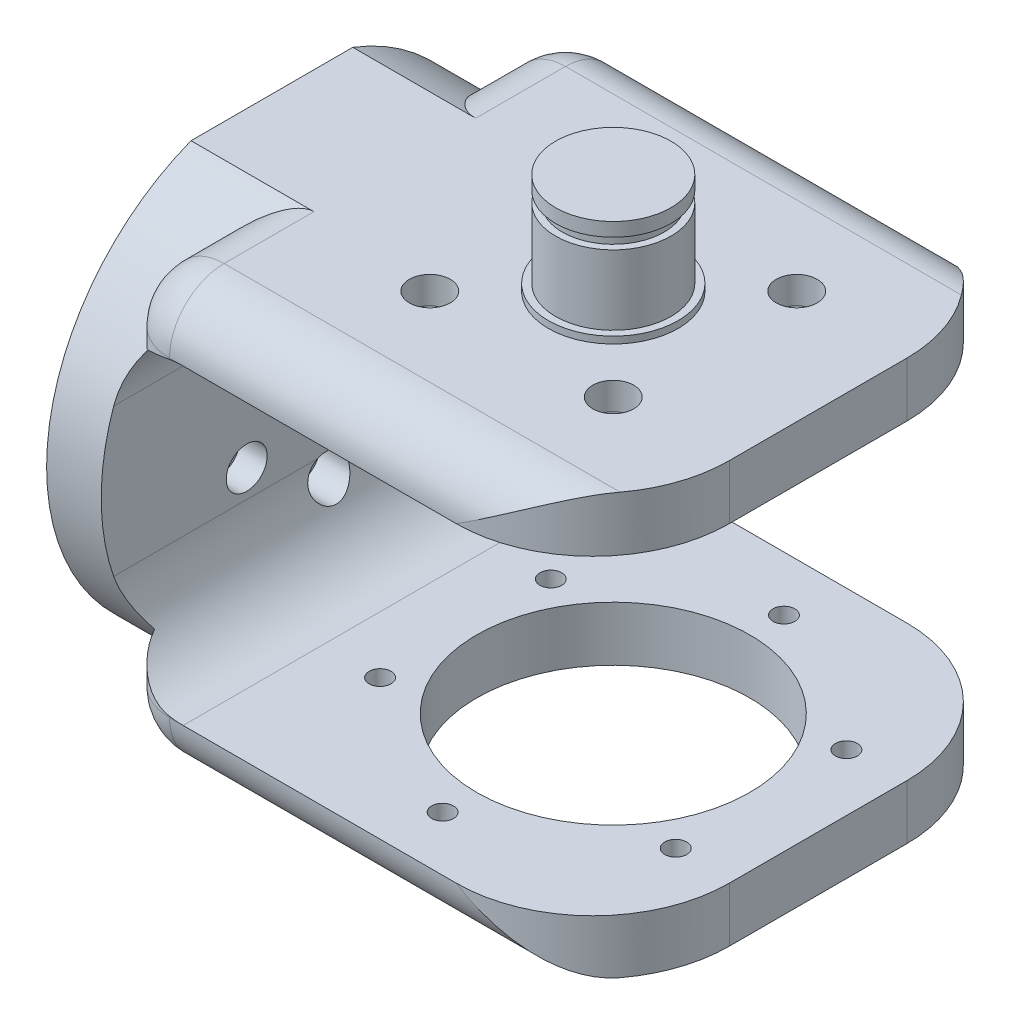
SolidWorks part; units mm, degrees
material "PETG-CF"
ref_plane "Front Plane" through (0, 0, 0) normal (0, 0, 1) x (1, 0, 0)
ref_plane "Top Plane" through (0, 0, 0) normal (0, 1, 0) x (1, 0, 0)
ref_plane "Right Plane" through (0, 0, 0) normal (1, 0, 0) x (0, 0, -1)
sketch "草图1" plane through (0, 0, 0) normal (0, 1, 0) x (1, 0, 0)
  line L1 (40, -33) -> (-40, -33)
  line L2 (40, -33) -> (40, 33)
  line L3 (40, 33) -> (-40, 33)
  line L4 (-40, -33) -> (-40, 33)
  line L5 (40, -33) -> (-40, 33) construction
  line L6 (40, 33) -> (-40, -33) construction
  point P0 (0, 0)
  dimension "D1" = 66
  dimension "D2" = 80
extrude "凸台-拉伸1" add sketch "草图1" along normal blind 8
sketch "草图2" plane through (0, 8, 0) normal (0, 1, 0) x (1, 0, 0)
  line L0 (-40, -33) -> (40, -33) construction
  line L1 (-32, -33) -> (-40, -33)
  line L2 (-32, -33) -> (-32, 33)
  line L3 (-32, 33) -> (-40, 33)
  line L4 (-40, -33) -> (-40, 33)
  line L5 (-32, -33) -> (-40, 33) construction
  line L6 (-32, 33) -> (-40, -33) construction
  point P0 (-36, 0)
  dimension "D1" = 8
extrude "凸台-拉伸2" add sketch "草图2" along normal blind 53.6
sketch "草图5" plane through (-32, 0, 0) normal (1, 0, 0) x (0, 0, -1)
  line L0 (-33, 61.6) -> (-33, 8) construction
  line L1 (33, 53.6) -> (-33, 53.6)
  line L2 (33, 53.6) -> (33, 61.6)
  line L3 (33, 61.6) -> (-33, 61.6)
  line L4 (-33, 53.6) -> (-33, 61.6)
  line L5 (33, 53.6) -> (-33, 61.6) construction
  line L6 (33, 61.6) -> (-33, 53.6) construction
  line L7 (33, 61.6) -> (33, 8) construction
  line L9 (-33, 61.6) -> (33, 61.6) construction
  point P0 (0, 57.6)
  dimension "D1" = 8
extrude "凸台-拉伸3" add sketch "草图5" along normal through all
sketch "草图4" plane through (0, 8, 0) normal (0, 1, 0) x (1, 0, 0)
  line L0 (-40, 33) -> (-40, -33) construction
  line L2 (40, -33) -> (40, 33) construction
  circle A0 centre (10, 0) radius 25 construction
  circle A1 centre (10, 25) radius 1.6
  circle A2 centre (-11.6506, 12.5) radius 1.6
  circle A3 centre (-11.6506, -12.5) radius 1.6
  circle A4 centre (10, -25) radius 1.6
  circle A5 centre (10, 0) radius 20
  circle A6 centre (31.6506, -12.5) radius 1.6
  circle A7 centre (31.6506, 12.5) radius 1.6
  point P17 (10, 0)
  point P22 (-40, 0)
  dimension "D3" = 50
  dimension "D4" = 3.2
  dimension "D6" = 40
  dimension "D1" = 30
  dimension "D5" = 6
extrude "切除-拉伸1" cut sketch "草图4" against normal through all contours A5 | A2 | A1 | A4 | A3 | A7 | A6
sketch "草图7" plane through (0, 61.6, 0) normal (0, 1, 0) x (1, 0, 0)
  line L0 (40, 33) -> (40, -33) construction
  line L2 (40, 33) -> (40, -33) construction
  line L3 (10, 0) -> (-3.435, 13.435) construction
  line L4 (10, 0) -> (10, 19) construction
  circle A0 centre (10, 0) radius 19 construction
  circle A5 centre (-3.435, 13.435) radius 1.6
  circle A6 centre (23.435, 13.435) radius 1.6
  circle A7 centre (23.435, -13.435) radius 1.6
  circle A8 centre (-3.435, -13.435) radius 1.6
  point P10 (40, 0)
  point P18 (10, 0)
  point P20 (10, 0)
  dimension "D1" = 38
  dimension "D4" = 45
  dimension "D5" = 3.2
  dimension "D3" = 30
  dimension "D6" = 4
extrude "切除-拉伸3" cut sketch "草图7" against normal up to next
sketch "草图8" plane through (0, 61.6, 0) normal (0, 1, 0) x (1, 0, 0)
  circle A0 centre (10, 0) radius 8.45
  dimension "D1" = 16.9
extrude "凸台-拉伸4" add sketch "草图8" along normal blind 14.8
ref_plane "基准面1" through (0, 74.4, 0) normal (0, 1, 0) x (1, 0, 0)
sketch "草图10" plane through (0, 74.4, 0) normal (0, 1, 0) x (1, 0, 0)
  circle A0 centre (10, 0) radius 8.45
  circle A1 centre (10, 0) radius 7.45
  dimension "D1" = 14.9
extrude "切除-拉伸4" cut sketch "草图10" against normal blind 1.6
ref_plane "基准面2" through (-36, 0, 0) normal (-1, 0, 0) x (0, 0, 1)
sketch "草图14" plane through (0, 61.6, 0) normal (0, 1, 0) x (1, 0, 0)
  circle A0 centre (-3.435, 13.435) radius 3
  circle A1 centre (23.435, 13.435) radius 3
  circle A2 centre (23.435, -13.435) radius 3
  circle A3 centre (-3.435, -13.435) radius 3
  point P12 (10, 0)
  dimension "D1" = 6
  dimension "D2" = 4
extrude "切除-拉伸6" cut sketch "草图14" against normal blind 4
sketch "草图15" plane through (0, 0, 0) normal (0, -1, 0) x (1, 0, 0)
  circle A0 centre (-11.6506, 12.5) radius 3
  circle A1 centre (10, 25) radius 3
  circle A2 centre (31.6506, 12.5) radius 3
  circle A3 centre (31.6506, -12.5) radius 3
  circle A4 centre (10, -25) radius 3
  circle A5 centre (-11.6506, -12.5) radius 3
  point P15 (10, 0)
  dimension "D1" = 6
  dimension "D2" = 6
extrude "切除-拉伸7" cut sketch "草图15" against normal blind 4
sketch "草图16" plane through (0, 61.6, 0) normal (0, 1, 0) x (1, 0, 0)
  circle A0 centre (10, 0) radius 9.5
  dimension "D1" = 19
extrude "凸台-拉伸5" add sketch "草图16" along normal blind 1
sketch "Sketch1" plane through (-40, 0, 0) normal (-1, 0, 0) x (0, 0, 1)
  line L0 (33, 61.6) -> (33, 0) construction
  circle A0 centre (0, 30.8) radius 18
  point P8 (33, 30.8)
  dimension "D1" = 36
extrude "Boss-Extrude1" add sketch "Sketch1" along normal blind 9.8
sketch "Sketch2" plane through (-49.8, 0, 0) normal (-1, 0, 0) x (0, 0, 1)
  circle A0 centre (0, 30.8) radius 13.5 construction
  circle A1 centre (0, 30.8) radius 4
  circle A2 centre (0, 17.3) radius 1.6
  circle A3 centre (-11.6913, 24.05) radius 1.6
  circle A4 centre (-11.6913, 37.55) radius 1.6
  circle A5 centre (0, 44.3) radius 1.6
  circle A6 centre (11.6913, 37.55) radius 1.6
  circle A7 centre (11.6913, 24.05) radius 1.6
  point P18 (0, 30.8)
  dimension "D1" = 27
  dimension "D2" = 8
  dimension "D3" = 3.2
  dimension "D4" = 6
extrude "Cut-Extrude1" cut sketch "Sketch2" against normal through all
sketch "Sketch4" plane through (-32, 0, 0) normal (1, 0, 0) x (0, 0, -1)
  circle A0 centre (0, 44.3) radius 3
  circle A1 centre (11.6913, 37.55) radius 3
  circle A2 centre (11.6913, 24.05) radius 3
  circle A3 centre (0, 17.3) radius 3
  circle A4 centre (-11.6913, 24.05) radius 3
  circle A5 centre (-11.6913, 37.55) radius 3
  point P15 (0, 30.8)
  dimension "D1" = 6
  dimension "D2" = 6
extrude "Cut-Extrude2" cut sketch "Sketch4" against normal blind 4
fillet "圆角4" radius 12 2 edges at (-32, 8, 0) (-32, 53.6, 0)
sketch "Sketch5" plane through (-40, 0, 0) normal (-1, 0, 0) x (0, 0, 1)
  line L1 (-33, 61.6) -> (33, 61.6)
  line L2 (-33, 61.6) -> (-33, 0)
  line L3 (-33, 0) -> (33, 0)
  line L4 (33, 61.6) -> (33, 0)
  circle A0 centre (0, 30.8) radius 33
  point P9 (33, 0)
  point P11 (-33, 61.6)
  line M7 (-33, 61.6) -> (-33, 0)
  line M9 (33, 0) -> (33, 61.6)
  line M11 (-33, 0) -> (33, 0)
  line M12 (33, 61.6) -> (-33, 61.6)
extrude "Cut-Extrude4" cut sketch "Sketch5" against normal blind 10 contours A0 M12 M7 | A0 L2 M11 | A0 M11 M9 | A0 L4 M12 region at (-40, 54.4726, -27.2664) region at (-40, 7.1274, -27.2664) region at (-40, 54.4726, 27.2664) region at (-40, 7.1274, 27.2664)
fillet "Fillet4" radius 8 4 edges at (5, 0, -33) (5, 0, 33) (5, 61.6, -33) (5, 61.6, 33)
fillet "Fillet5" radius 8 12 edges at (-30, 10.6834, -33) (-30, 0, -18.4237) (-30, 61.6, -18.4237) (-30, 50.9166, -33) (-30, 0, 18.4237) (-30, 10.6834, 33) (-30, 50.9166, 33) (-30, 61.6, 18.4237) (-30, 2.3431, -30.6569) (-30, 59.2569, -30.6569) (-30, 2.3431, 30.6569) (-30, 59.2569, 30.6569)
sketch "Sketch6" plane through (0, 0, 0) normal (0, -1, 0) x (-1, 0, 0)
  line L1 (22, -33) -> (-20, -33)
  line L2 (22, -33) -> (22, 33)
  line L3 (22, 33) -> (-20, 33)
  line L4 (-40, -13) -> (-40, 13)
  line L5 (22, -33) -> (-40, -33)
  line L6 (22, -33) -> (22, 33)
  line L7 (22, 33) -> (-40, 33)
  line L8 (-40, -33) -> (-40, 33)
  arc A0 (-20, 33) -> (-40, 13) centre (-20, 13) ccw
  arc A1 (-20, -33) -> (-40, -13) centre (-20, -13) cw
  point P8 (-40, 33)
  line M12 (-13, 25) -> (-40, 25)
  line M13 (-40, 25) -> (-40, -25)
  line M14 (-40, -25) -> (-13, -25)
  dimension "D1" = 20
extrude "Cut-Extrude5" cut sketch "Sketch6" against normal up to surface (61.6 mm away) contours L5 A1 L8 M14 | A1 M14 M13 | A0 M12 M13 | A0 L7 L8 M12 region at (34.8188, 0, 29.9358) region at (38.8238, 0, 22.0633) region at (34.8188, 0, -29.9358) region at (38.8238, 0, -22.0633) up to face at (10, 61.6, 9.5)
